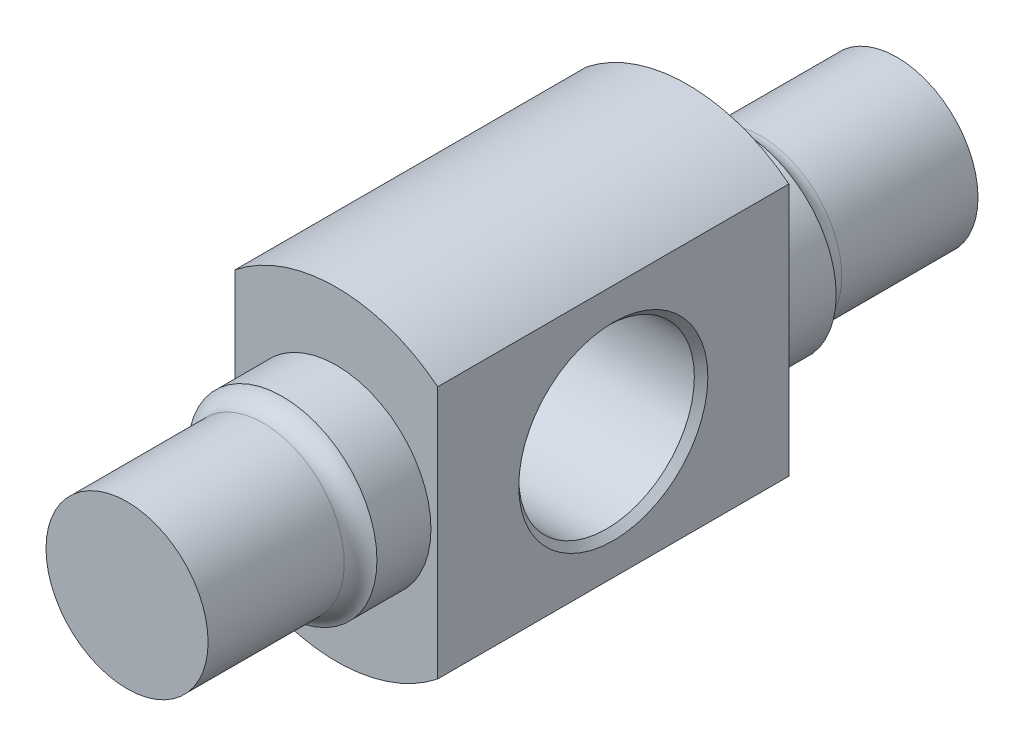
SolidWorks part; units mm, degrees
ref_plane "Piano frontale" through (0, 0, 0) normal (0, 0, 1) x (1, 0, 0)
ref_plane "Piano superiore" through (0, 0, 0) normal (0, 1, 0) x (1, 0, 0)
ref_plane "Piano destro" through (0, 0, 0) normal (1, 0, 0) x (0, 0, -1)
sketch "Schizzo1" plane through (0, 0, 0) normal (0, 0, 1) x (1, 0, 0)
  line L0 (-7.5, 0) -> (7.5, 0) construction
  line L1 (-7.5, -9.3675) -> (-7.5, 9.3675)
  line L2 (7.5, -9.3675) -> (7.5, 9.3675)
  arc A0 (-7.5, -9.3675) -> (7.5, -9.3675) centre (0, 0) ccw
  arc A1 (7.5, 9.3675) -> (-7.5, 9.3675) centre (0, 0) ccw
  point P4 (0, 0)
  point P7 (-7.5, 0)
  point P11 (7.5, 0)
  point P13 (-7.5, 9.3675)
  point P14 (7.5, 9.3675)
  dimension "D2" = 24
  dimension "D1" = 15
extrude "Estrusione-Estrusione1" add sketch "Schizzo1" along normal mid plane 26
sketch "Schizzo2" plane through (7.5, 0, 0) normal (1, 0, 0) x (0, 0, -1)
  circle A0 centre (0, 0) radius 6.5
  dimension "D1" = 13
extrude "Taglio-Estrusione1" cut sketch "Schizzo2" against normal through all both and the other way through all
chamfer "Smusso1" distance 0.5 angle 45 2 edges at (-7.5, 6.5, 0) (7.5, -6.5, 0)
sketch "Schizzo3" plane through (0, 0, 13) normal (0, 0, 1) x (1, 0, 0)
  circle A0 centre (0, 0) radius 7
  dimension "D1" = 14
extrude "Estrusione-Estrusione2" add sketch "Schizzo3" along normal blind 4
sketch "Schizzo5" plane through (0, 0, 17) normal (0, 0, 1) x (1, 0, 0)
  circle A0 centre (0, 0) radius 6
  dimension "D1" = 12
extrude "Estrusione-Estrusione3" add sketch "Schizzo5" along normal blind 11.5
cosmetic thread "Filettatura cosmetica1" parameters "D2"=10.072
fillet "Raccordo1" radius 1.5 1 edges at (6, 0, 17)
mirror "Specchia1" about plane through (0, 0, 0) normal (0, 0, 1) of "Estrusione-Estrusione3", "Raccordo1", "Estrusione-Estrusione2"
cosmetic thread "Filettatura cosmetica2" parameters "D2"=10.072
